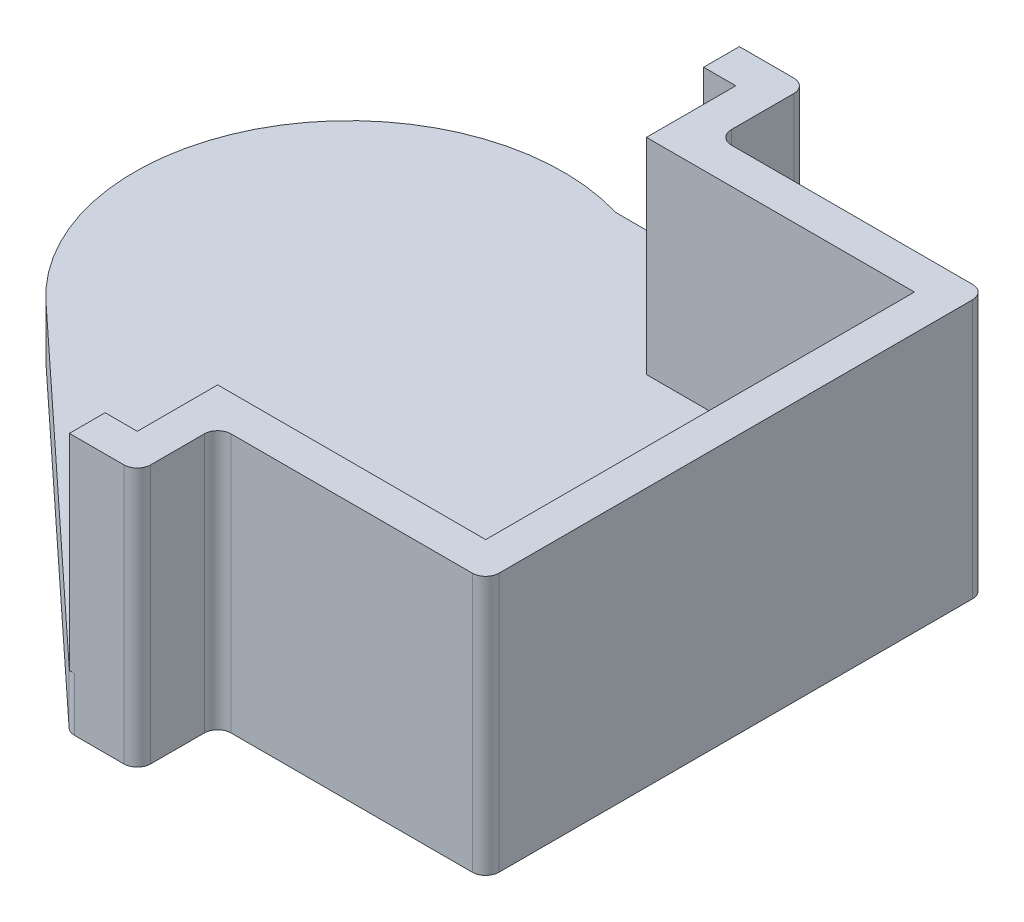
SolidWorks part; units mm, degrees
ref_plane "Front Plane" through (0, 0, 0) normal (0, 0, 1) x (1, 0, 0)
ref_plane "Top Plane" through (0, 0, 0) normal (0, 1, 0) x (1, 0, 0)
ref_plane "Right Plane" through (0, 0, 0) normal (1, 0, 0) x (0, 0, -1)
sketch "Sketch1" plane through (0, 0, 0) normal (0, 1, 0) x (1, 0, 0)
  line L0 (3.35, 28) -> (3.35, 23)
  line L9 (0, 0) -> (3.35, 0)
  line L10 (0, 0) -> (0, 23)
  line L11 (0, 23) -> (3.35, 23)
  line L12 (19.65, 0) -> (19.65, 23)
  line L14 (4.65, 0) -> (4.65, -5)
  line L15 (4.65, -5) -> (3.35, -5)
  line L16 (3.35, 0) -> (3.35, -5)
  line L17 (4.65, -5) -> (3.35, -5)
  line L18 (4.65, -5) -> (4.65, 28) construction
  line L19 (4.65, 28) -> (3.35, 28)
  line L20 (3.35, -5) -> (3.35, 28) construction
  line L21 (4.65, 28) -> (4.65, 23)
  line L22 (4.65, 0) -> (19.65, 0)
  line L23 (4.65, 23) -> (19.65, 23)
  line L24 (2.85, 28) -> (2.85, 23.5)
  line L25 (-0.5, 23.5) -> (2.85, 23.5)
  line L26 (-0.5, -0.5) -> (-0.5, 23.5)
  line L27 (-0.5, -0.5) -> (2.85, -0.5)
  line L28 (2.85, -0.5) -> (2.85, -5)
  line L29 (5.15, -0.5) -> (5.15, -5)
  line L30 (5.15, -0.5) -> (20.15, -0.5)
  line L31 (20.15, -0.5) -> (20.15, 23.5)
  line L32 (5.15, 23.5) -> (20.15, 23.5)
  line L33 (5.15, 28) -> (5.15, 23.5)
  line L34 (4.65, -4.5) -> (3.35, -4.5)
  line L35 (4.65, -4.5) -> (3.35, -4.5)
  line L37 (5.15, -5) -> (5.15, 28)
  line L38 (3.85, -5) -> (3.85, 28)
  line L39 (2.85, -5) -> (3.35, -5)
  line L40 (5.15, -5) -> (4.65, -5)
  line L41 (3.35, 28) -> (5.15, 28)
  line L42 (4.65, 28) -> (3.35, 28)
  line L43 (5.15, 28) -> (5.15, 28.5)
  line L46 (2.85, 28) -> (2.85, 28.5)
  line L47 (2.85, 28.5) -> (5.15, 28.5)
  line L48 (5.15, 28) -> (5.15, 28.5)
  dimension "D1" = 23
  dimension "D2" = 19.65
  dimension "D3" = 15
  dimension "D4" = 1.3
  dimension "D5" = 5
  dimension "D6" = 5
  dimension "D7" = 0.5
sketch "Sketch3" plane through (0, 0, 0) normal (0, 1, 0) x (1, 0, 0)
  line L1 (3.35, -5) -> (7.15, -5)
  line L2 (3.35, -5) -> (3.35, 28)
  line L3 (3.35, 28) -> (7.15, 28)
  line L4 (7.15, -5) -> (7.15, -2.5)
  line L5 (4.65, 28) -> (3.35, 28) construction
  line L6 (7.15, 25.5) -> (7.15, 28)
  line L7 (4.65, -5) -> (3.35, -5) construction
  line L8 (7.15, 25.5) -> (22.15, 25.5)
  line L10 (7.15, -2.5) -> (22.15, -2.5)
  line L11 (22.15, 25.5) -> (22.15, -2.5)
  line L12 (4.65, 23) -> (19.65, 23) construction
  line L13 (19.65, 0) -> (19.65, 23) construction
  line L14 (4.65, 0) -> (19.65, 0) construction
  line L15 (4.65, 0) -> (4.65, -5) construction
  point P20 (7.15, -3.75)
  dimension "D1" = 2.5
  dimension "D2" = 2.5
  dimension "D3" = 2.5
  dimension "D4" = 2.5
sketch "Sketch9" plane through (0, 0, 0) normal (0, 1, 0) x (1, 0, 0)
  line L0 (3.35, 28) -> (3.35, 23)
  line L9 (0, 0) -> (3.35, 0)
  line L10 (0, 0) -> (0, 23)
  line L11 (0, 23) -> (3.35, 23)
  line L12 (19.65, 0) -> (19.65, 23)
  line L14 (4.65, 0) -> (4.65, -4.5)
  line L15 (4.65, -5) -> (3.35, -5)
  line L16 (3.35, 0) -> (3.35, -4.5)
  line L17 (4.65, -5) -> (3.35, -5)
  line L18 (4.65, -4.5) -> (4.65, 28) construction
  line L19 (4.65, 28) -> (3.35, 28)
  line L20 (3.35, -4.5) -> (3.35, 28) construction
  line L21 (4.65, 28) -> (4.65, 23)
  line L22 (4.65, 0) -> (19.65, 0)
  line L23 (4.65, 23) -> (19.65, 23)
  line L24 (4.65, 28) -> (3.35, 28)
  line L25 (5.15, -5) -> (3.35, -5)
  line L26 (7.15, -5) -> (7.15, -6.25)
  line L27 (6.4, -7) -> (3.35, -7)
  line L28 (3.35, -5) -> (3.35, -7)
  line L29 (5.15, -0.5) -> (5.15, -5)
  line L30 (5.15, -0.5) -> (20.15, -0.5)
  line L31 (20.15, -0.5) -> (20.15, 23.5)
  line L32 (5.15, 23.5) -> (20.15, 23.5)
  line L33 (5.15, 28) -> (5.15, 23.5)
  line L34 (4.65, -4.5) -> (3.35, -4.5)
  line L35 (4.65, -4.5) -> (3.35, -4.5)
  line L36 (7.15, 28) -> (7.15, 26.25)
  line L37 (5.15, -5) -> (5.15, -0.5)
  line L38 (3.35, -5) -> (3.35, -7)
  line L40 (5.15, -5) -> (4.65, -5)
  line L41 (3.35, 28) -> (4.65, 28)
  line L42 (4.65, 28) -> (3.35, 28)
  line L43 (5.15, 28) -> (5.15, 28.5)
  line L47 (3.35, 30.5) -> (5.15, 30.5)
  line L48 (5.15, 28) -> (5.15, 28.5)
  line L49 (7.9, 25.5) -> (21.4, 25.5)
  line L50 (22.15, -1.75) -> (22.15, 24.75)
  line L51 (7.9, -2.5) -> (21.4, -2.5)
  line L52 (7.15, -3.25) -> (7.15, -5)
  line L53 (5.15, 23.5) -> (5.15, 28)
  line L54 (7.15, 28) -> (7.15, 29.75)
  line L55 (6.4, 30.5) -> (3.35, 30.5)
  line L57 (5.15, -5) -> (5.15, 28) construction
  line L58 (7.15, -2.5) -> (22.15, -2.5) construction
  line L60 (3.35, 30.5) -> (5.15, 30.5)
  line L61 (3.35, 30.5) -> (3.35, 28.5)
  line L62 (3.35, 28.5) -> (5.15, 28.5)
  line L64 (4.65, 0) -> (4.65, -5) construction
  line L65 (4.65, -5) -> (4.65, 28) construction
  line L66 (7.15, -2.5) -> (7.15, -5) construction
  line L67 (7.15, 28) -> (7.15, 25.5) construction
  line L68 (7.15, 25.5) -> (22.15, 25.5) construction
  line L69 (22.15, -2.5) -> (22.15, 25.5) construction
  arc A0 (7.9, -2.5) -> (7.15, -3.25) centre (7.9, -3.25) ccw
  arc A1 (7.15, 26.25) -> (7.9, 25.5) centre (7.9, 26.25) ccw
  arc A2 (7.15, 29.75) -> (6.4, 30.5) centre (6.4, 29.75) ccw
  arc A3 (21.4, 25.5) -> (22.15, 24.75) centre (21.4, 24.75) cw
  arc A4 (22.15, -1.75) -> (21.4, -2.5) centre (21.4, -1.75) cw
  arc A5 (7.15, -6.25) -> (6.4, -7) centre (6.4, -6.25) cw
  dimension "D10" = 0.75
  dimension "D1" = 23
  dimension "D2" = 19.65
  dimension "D3" = 15
  dimension "D4" = 1.3
  dimension "D5" = 5
  dimension "D6" = 5
  dimension "D7" = 0.5
  dimension "D8" = 2.5
  dimension "D9" = 2
  dimension "D11" = 0.5
extrude "Bracket" add sketch "Sketch9" along normal blind 11.5 contours L61 L62 L43 L33 L32 L31 L30 L29 L25 L15 L28 L27 L26 L52 L51 L50 L49 L36 L54 L55 L47 region at (4.9, 0, 5.4195)
sketch "Sketch12" plane through (0, 0, 0) normal (0, 1, 0) x (1, 0, 0)
  line L0 (3.1341, -6.7994) -> (-15.1691, 10.209)
  line L2 (-3.4667, 30.5) -> (6.4, 30.5)
  line L3 (7.15, 29.75) -> (7.15, 26.25)
  line L4 (7.9, 25.5) -> (21.4, 25.5)
  line L5 (22.15, 24.75) -> (22.15, -1.75)
  line L6 (21.4, -2.5) -> (7.9, -2.5)
  line L7 (7.15, -3.25) -> (7.15, -6.25)
  line L8 (6.4, -7) -> (3.6447, -7)
  arc A0 (-3.6746, 30.5294) -> (-15.1691, 10.209) centre (-7.0005, 18.9995) ccw
  arc A1 (3.1341, -6.7994) -> (3.6447, -7) centre (3.6447, -6.25) ccw
  arc A2 (7.15, -6.25) -> (6.4, -7) centre (6.4, -6.25) cw
  arc A3 (7.9, -2.5) -> (7.15, -3.25) centre (7.9, -3.25) ccw
  arc A4 (22.15, -1.75) -> (21.4, -2.5) centre (21.4, -1.75) cw
  arc A5 (21.4, 25.5) -> (22.15, 24.75) centre (21.4, 24.75) cw
  arc A6 (7.15, 26.25) -> (7.9, 25.5) centre (7.9, 26.25) ccw
  arc A7 (6.4, 30.5) -> (7.15, 29.75) centre (6.4, 29.75) cw
  arc A8 (-3.4667, 30.5) -> (-3.6746, 30.5294) centre (-3.4667, 31.25) cw
  point P17 (3.35, -7)
  point P22 (7.15, -2.5)
  point P25 (22.15, -2.5)
  point P28 (22.15, 25.5)
  point P31 (7.15, 25.5)
  point P36 (0, 0)
  dimension "D1" = 0.75
extrude "Boss-Extrude1" add sketch "Sketch12" against normal blind 3
sketch "Sketch15" plane through (0, 0, 0) normal (0, 1, 0) x (1, 0, 0)
  circle A1 centre (-7, 19) radius 7.0711
  circle A2 centre (-7, 26.0711) radius 2
  circle A3 centre (0.0711, 19) radius 2
  circle A4 centre (-7, 11.9289) radius 2
  circle A5 centre (-14.0711, 19) radius 2
  point P0 (-7, 19)
  point P9 (-7, 19)
  point P12 (-7, 19)
  point P15 (-7, 19)
  point P18 (-7, 19)
  dimension "D1" = 4
extrude "Boss-Extrude2" add sketch "Sketch15" against normal blind 3.5 from surface contours A5 | A2 | A4 | A3 starting at face at (7.1197, -3, -11.8189)
